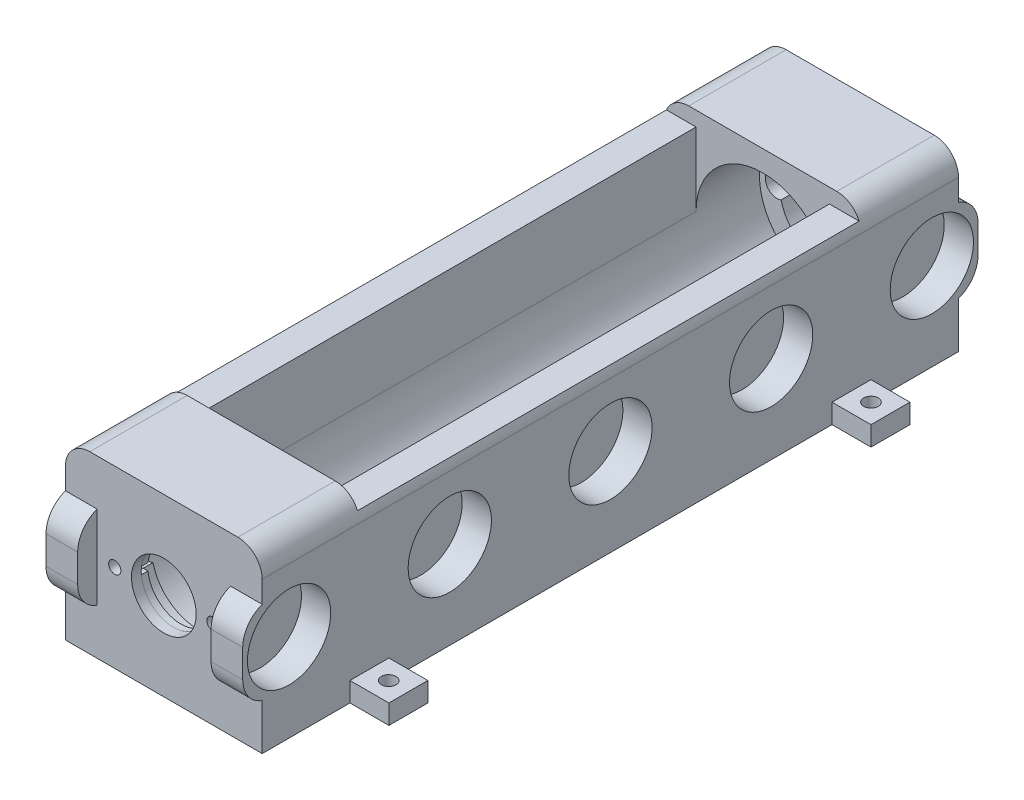
SolidWorks part; units mm, degrees
ref_plane "Alzado" through (0, 0, 0) normal (0, 0, 1) x (1, 0, 0)
ref_plane "Planta" through (0, 0, 0) normal (0, 1, 0) x (1, 0, 0)
ref_plane "Vista lateral" through (0, 0, 0) normal (1, 0, 0) x (0, 0, -1)
sketch "Croquis1" plane through (0, 0, 0) normal (0, 0, 1) x (1, 0, 0)
  line L0 (0, 8.3596) -> (0, -1.3417) construction
  line L1 (9, 0.75) -> (-9, 0.75)
  line L2 (0, 0.75) -> (0, -0.75)
  line L3 (9, -0.75) -> (-9, -0.75)
  line L4 (-9, 0.75) -> (-9, -0.75)
  line L5 (-12.48, 10.7299) -> (-12.48, -4.9079) construction
  line L6 (9, 0.75) -> (9, -0.75)
  line L7 (0, 0) -> (-17.6562, 0) construction
  circle A0 centre (-10.08, 0) radius 2.4
  circle A1 centre (-10.08, 0) radius 0.9
  circle A2 centre (10.08, 0) radius 0.9
  circle A3 centre (10.08, 0) radius 2.4
  circle A4 centre (0, 0) radius 13.7
  point P9 (0, 0)
  dimension "D1" = 1.8
  dimension "D4" = 4.8
  dimension "D6" = 27.4
  dimension "D2" = 1.5
  dimension "D3" = 9
  dimension "D5" = 12.48
extrude "Saliente-Extruir1" add sketch "Croquis1" along normal blind 5 contours A4 L1 A3 L3 A0 region at (-13.3125, 0, 0)
sketch "Croquis2" plane through (0, 0, 5) normal (0, 0, 1) x (1, 0, 0)
  circle A0 centre (0, 0) radius 9.5
  dimension "D1" = 19
extrude "Cortar-Extruir1" cut sketch "Croquis2" against normal blind 3.5
sketch "Croquis3" plane through (0, 0, 1.5) normal (0, 0, 1) x (1, 0, 0)
  circle A0 centre (0, 0) radius 6.8
  dimension "D1" = 13.6
extrude "Cortar-Extruir2" cut sketch "Croquis3" against normal blind 3
sketch "Croquis4" plane through (0, 0, 0) normal (0, 0, -1) x (-1, 0, 0)
  circle A0 centre (0, 0) radius 13.7 construction
  circle A1 centre (0, 0) radius 13.7
  circle A2 centre (0, 0) radius 6.65
  dimension "D1" = 13.3
extrude "Saliente-Extruir2" add sketch "Croquis4" along normal blind 2
sketch "Croquis5" plane through (0, 0, 5) normal (0, 0, 1) x (1, 0, 0)
  circle A0 centre (-10.08, 0) radius 1.25
  circle A1 centre (10.08, 0) radius 1.25
  dimension "D1" = 2.5
  dimension "D2" = 2.5
extrude "Cortar-Extruir3" cut sketch "Croquis5" against normal through all
sketch "Croquis6" plane through (0, 0, -2) normal (0, 0, -1) x (-1, 0, 0)
  line L1 (-20.2, -18) -> (20.2, -18)
  line L2 (-20.2, -18) -> (-20.2, 18)
  line L3 (-20.2, 18) -> (20.2, 18)
  line L4 (20.2, -18) -> (20.2, 18)
  line L5 (-20.2, -18) -> (20.2, 18) construction
  line L6 (-20.2, 18) -> (20.2, -18) construction
  circle A0 centre (0, 0) radius 13.7 construction
  circle A1 centre (0, 0) radius 13.7
  point P0 (0, 0)
  dimension "D1" = 36
  dimension "D2" = 40.4
extrude "Saliente-Extruir3" add sketch "Croquis6" against normal blind 20 separate body
sketch "Croquis8" plane through (0, 0, 18) normal (0, 0, 1) x (1, 0, 0)
  line L0 (-13.7, 0) -> (-13.7, 15)
  line L1 (-13.7, 15) -> (20.2, 15)
  line L2 (13.7, 0) -> (13.7, 15)
  line L3 (13.7, 15) -> (-20.2, 15)
  line L4 (-20.2, 18) -> (-20.2, -18)
  line L5 (20.2, 18) -> (-20.2, 18)
  line L6 (20.2, -18) -> (20.2, 18)
  line L7 (-20.2, -18) -> (20.2, -18)
  line L8 (-20.2, 18) -> (-20.2, 15)
  line L10 (20.2, 15) -> (20.2, 18)
  line L11 (-20.2, -18) -> (20.2, -18)
  line L12 (20.2, 18) -> (20.2, -18) construction
  line L13 (27.021, 0) -> (-27.7174, 0) construction
  circle A0 centre (0, 0) radius 13.7 construction
  circle A1 centre (0, 0) radius 13.7 construction
  arc A2 (-13.7, 0) -> (13.7, 0) centre (0, 0) ccw
  circle M15 centre (0, 0) radius 13.7
  line M16 (-20.2, 18) -> (-20.2, -18)
  line M17 (-20.2, -18) -> (20.2, -18)
  line M18 (20.2, -18) -> (20.2, 18)
  dimension "D2" = 15
  dimension "D3" = 15
  dimension "D1" = 0
extrude "Saliente-Extruir5" add sketch "Croquis8" along normal blind 51.5 contours L13 M18 M15 M16 M17 | L13 L0 L3 M16 | L13 L1 L2 M18 region at (-16.95, 7.5, 18) region at (0, -14.1423, 18) region at (16.95, 7.5, 18)
sketch "Croquis11" plane through (0, 0, -2) normal (0, 0, -1) x (-1, 0, 0)
  line L0 (25.6797, 0) -> (-27.0718, 0) construction
  line L1 (-20.2, 8.55) -> (-13.7, 8.55)
  line L2 (-20.2, 8.55) -> (-20.2, -8.55)
  line L3 (-20.2, -8.55) -> (-13.7, -8.55)
  line L4 (-13.7, 8.55) -> (-13.7, -8.55)
  line L5 (0, 15.867) -> (0, -22.027) construction
  line L6 (20.2, -8.55) -> (13.7, -8.55)
  line L7 (13.7, 8.55) -> (13.7, -8.55)
  line L8 (20.2, 8.55) -> (13.7, 8.55)
  line L9 (20.2, 8.55) -> (20.2, -8.55)
  circle A0 centre (0, 0) radius 13.7 construction
  dimension "D1" = 17.1
  dimension "D2" = 6.5
extrude "Saliente-Extruir6" add sketch "Croquis11" along normal blind 4
ref_plane "Plano1" through (0, 0, 69.5) normal (0, 0, 1) x (1, 0, 0)
mirror "Simetría10" about plane through (0, 0, 69.5) normal (0, 0, 1) of bodies 126 105 108
sketch "Croquis9" plane through (-20.2, 0, 0) normal (-1, 0, 0) x (0, 0, 1)
  line L0 (0, 0) -> (156.1517, 0) construction
  line L1 (69.5, -18) -> (-2, -18) construction
  circle A0 centre (3.4791, 0) radius 8.55
  circle A1 centre (3.4791, 0) radius 16.5 construction
  circle A2 centre (36.4791, 0) radius 16.5 construction
  circle A3 centre (69.4791, 0) radius 16.5 construction
  circle A4 centre (102.4791, 0) radius 16.5 construction
  circle A5 centre (135.4791, 0) radius 16.5 construction
  circle A6 centre (36.4791, 0) radius 8.55
  circle A7 centre (69.4791, 0) radius 8.55
  circle A8 centre (102.4791, 0) radius 8.55
  circle A9 centre (135.4791, 0) radius 8.55
  dimension "D1" = 17.1
  dimension "D3" = 33
  dimension "D2" = 3.4791
extrude "Cortar-Extruir4" cut sketch "Croquis9" against normal blind 6
mirror "Simetría11" about plane through (0, 0, 0) normal (1, 0, 0) of "Cortar-Extruir4"
fillet "Redondeo1" radius 5 2 edges at (20.2, 18, 8) (-20.2, 18, 8)
fillet "Redondeo2" radius 5 2 edges at (20.2, 18, 131) (-20.2, 18, 131)
ref_plane "Plano2" [suppressed] through (0, -13.7, 0) normal (0, 1, 0) x (1, 0, 0)
sketch "Croquis10" plane through (0, 0, 0) normal (0, -1, 0) x (1, 0, 0)
  line L0 (0, -25.2789) -> (0, 143.4615) construction
  circle A0 centre (0, 60) radius 4
  circle A1 centre (0, 105) radius 4
  circle A2 centre (0, 80) radius 4
  circle A3 centre (0, 25) radius 4
  dimension "D1" = 8
  dimension "D2" = 25
  dimension "D3" = 35
  dimension "D4" = 20
  dimension "D5" = 25
extrude "Cortar-Extruir5" cut sketch "Croquis10" along normal blind 16
sketch "Croquis12" plane through (0, 0, 0) normal (0, -1, 0) x (1, 0, 0)
  line L0 (0, -25.2789) -> (0, 143.4615) construction
  circle A0 centre (0, 60) radius 2
  circle A1 centre (0, 105) radius 2
  circle A2 centre (0, 80) radius 2
  circle A3 centre (0, 25) radius 2
  dimension "D1" = 4
  dimension "D2" = 25
  dimension "D3" = 35
  dimension "D4" = 20
  dimension "D5" = 25
extrude "Cortar-Extruir6" cut sketch "Croquis12" along normal blind 24
fillet "Redondeo4" radius 6 4 edges at (-16.95, -8.55, 145) (-16.95, 8.55, 145) (16.95, -8.55, 145) (16.95, 8.55, 145)
fillet "Redondeo5" radius 6 4 edges at (-16.95, -8.55, -6) (-16.95, 8.55, -6) (16.95, -8.55, -6) (16.95, 8.55, -6)
sketch "Croquis13" plane through (-20.2, 0, 0) normal (-1, 0, 0) x (0, 0, 1)
  line L0 (69.5, -18) -> (-2, -18) construction
  line L1 (15.9791, -18) -> (23.9791, -18)
  line L2 (15.9791, -18) -> (15.9791, -14)
  line L3 (15.9791, -14) -> (23.9791, -14)
  line L4 (23.9791, -18) -> (23.9791, -14)
  line L5 (36.4791, 0) -> (3.4791, 0) construction
  line L6 (19.9791, 5.9902) -> (19.9791, -22.7895) construction
  line L7 (69.4791, 0) -> (69.4791, 24.455) construction
  line L10 (122.9791, -14) -> (114.9791, -14)
  line L11 (114.9791, -18) -> (114.9791, -14)
  line L12 (122.9791, -18) -> (114.9791, -18)
  line L13 (122.9791, -18) -> (122.9791, -14)
  point P12 (19.9791, 0)
  dimension "D1" = 4
  dimension "D2" = 8
extrude "Saliente-Extruir7" add sketch "Croquis13" along normal blind 8
sketch "Croquis14" plane through (0, -14, 0) normal (0, 1, 0) x (1, 0, 0)
  line L0 (-24.2, -15.9791) -> (-24.2, -23.9791) construction
  line L1 (-28.2, -15.9791) -> (-20.2, -15.9791) construction
  line L2 (-28.2, -23.9791) -> (-20.2, -23.9791) construction
  line L3 (-28.2, -19.9791) -> (-20.2, -19.9791) construction
  line L4 (-28.2, -23.9791) -> (-28.2, -15.9791) construction
  line L5 (-20.2, -23.9791) -> (-20.2, -15.9791) construction
  line L6 (88.2515, -69.5) -> (-51.7311, -69.5) construction
  line L7 (-18.15, -69.5) -> (18.15, -69.5) construction
  circle A0 centre (-24.2, -19.9791) radius 1.5
  circle A1 centre (-24.2, -119.0209) radius 1.5
  dimension "D1" = 3
extrude "Cortar-Extruir7" cut sketch "Croquis14" against normal blind 8
mirror "Simetría12" about plane through (0, 0, 0) normal (1, 0, 0) of "Saliente-Extruir7", "Cortar-Extruir7"
